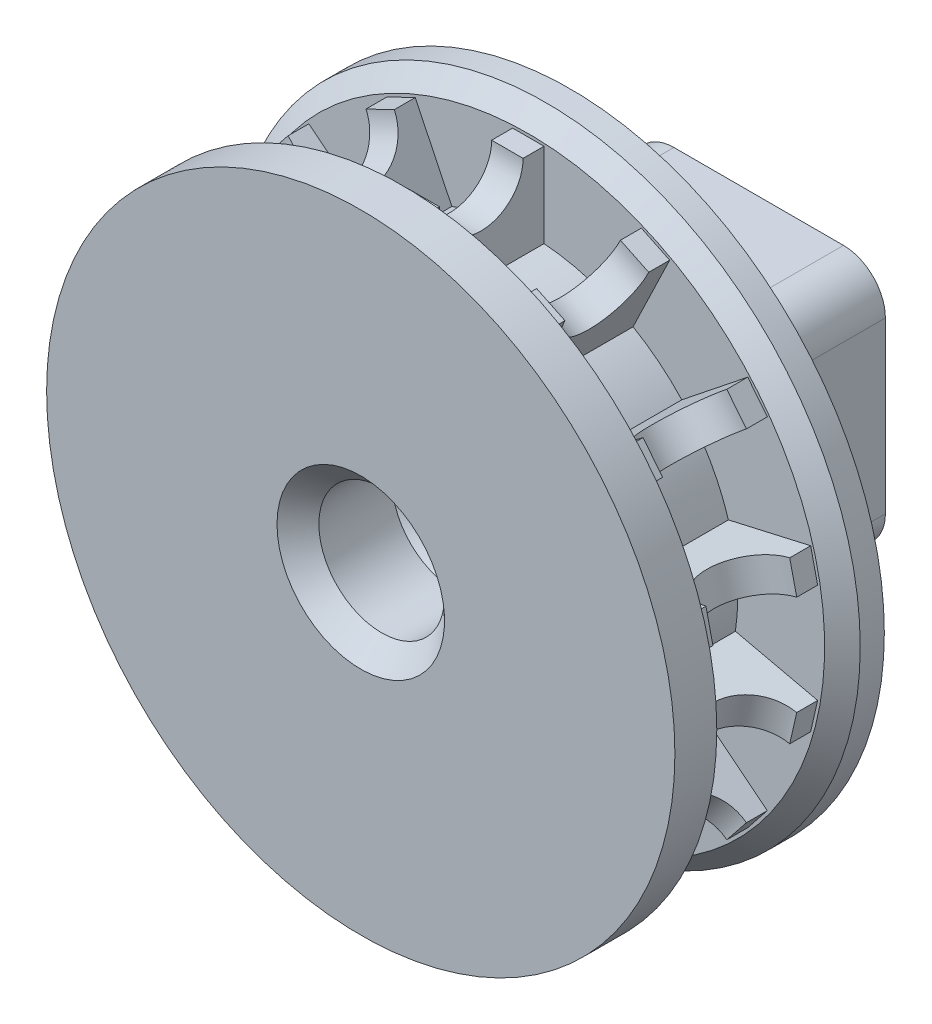
SolidWorks part; units mm, degrees
ref_plane "前基準面" through (0, 0, 0) normal (0, 0, 1) x (1, 0, 0)
ref_plane "上基準面" through (0, 0, 0) normal (0, 1, 0) x (1, 0, 0)
ref_plane "右基準面" through (0, 0, 0) normal (1, 0, 0) x (0, 0, -1)
ref_axis "基準軸1" through (0, 0, 5.5) along (0, 0, -1)
sketch "草圖1" plane through (0, 0, 0) normal (1, 0, 0) x (0, 0, -1)
  line L0 (-5, 0) -> (5, 0)
  line L1 (5, 0) -> (5, 15)
  line L2 (5, 15) -> (3, 15)
  line L3 (3, 15) -> (3, 10)
  line L4 (3, 10) -> (-3, 10)
  line L5 (-3, 10) -> (-3, 15)
  line L6 (-3, 15) -> (-5, 15)
  line L7 (-5, 15) -> (-5, 0)
  line L8 (0, 0) -> (0, 10) construction
  dimension "D1" = 10
  dimension "D2" = 2
  dimension "D3" = 15
  dimension "D4" = 10
revolve "旋轉1" add sketch "草圖1" angle 360 about L0
sketch "草圖2" plane through (0, 0, 0) normal (1, 0, 0) x (0, 0, -1)
  line L0 (-3, 10) -> (3, 10) construction
  line L1 (3, 10) -> (3, 14)
  line L2 (3, 15) -> (3, -15) construction
  line L3 (3, 14) -> (-3, 14) construction
  line L4 (-3, -15) -> (-3, 15) construction
  line L5 (-3, 14) -> (-3, 10)
  line L6 (-2, 14) -> (-3, 14)
  line L7 (2, 14) -> (3, 14)
  line L8 (-3, 10) -> (-3, 8.5)
  line L9 (-3, 8.5) -> (3, 8.5)
  line L10 (3, 8.5) -> (3, 10)
  arc A0 (-2, 14) -> (2, 14) centre (0, 14) ccw
  dimension "D2" = 2
  dimension "D1" = 4
  dimension "D3" = 1.5
extrude "填料-伸長1" add sketch "草圖2" along normal mid plane 1.5
pattern_circular "環狀複製排列1" count 14 over 360 about axis through (0, 0, 5.5) along (0, 0, -1) of "填料-伸長1"
sketch "草圖3" plane through (0, 0, -5) normal (0, 0, -1) x (-1, 0, 0)
  line L1 (-3.05, -3.05) -> (3.05, -3.05)
  line L2 (-3.05, -3.05) -> (-3.05, 3.05)
  line L3 (-3.05, 3.05) -> (3.05, 3.05)
  line L4 (3.05, -3.05) -> (3.05, 3.05)
  line L5 (-3.05, -3.05) -> (3.05, 3.05) construction
  line L6 (-3.05, 3.05) -> (3.05, -3.05) construction
  line L7 (-4.05, -6.05) -> (4.05, -6.05)
  line L8 (-6.05, -4.05) -> (-6.05, 4.05)
  line L9 (-4.05, 6.05) -> (4.05, 6.05)
  line L10 (6.05, -4.05) -> (6.05, 4.05)
  line L11 (-6.05, -6.05) -> (6.05, 6.05) construction
  line L12 (-6.05, 6.05) -> (6.05, -6.05) construction
  arc A0 (-4.05, -6.05) -> (-6.05, -4.05) centre (-4.05, -4.05) cw
  arc A1 (4.05, -6.05) -> (6.05, -4.05) centre (4.05, -4.05) ccw
  arc A2 (4.05, 6.05) -> (6.05, 4.05) centre (4.05, 4.05) cw
  arc A3 (-6.05, 4.05) -> (-4.05, 6.05) centre (-4.05, 4.05) cw
  point P0 (0, 0)
  point P6 (0, 0)
  dimension "D3" = 2
  dimension "D1" = 6.1
  dimension "D2" = 3
extrude "填料-伸長2" add sketch "草圖3" along normal blind 9
fillet "圓角1" radius 2 8 edges at (0, 6.05, -5) (-5.4642, 5.4642, -5) (-6.05, 0, -5) (-5.4642, -5.4642, -5) (0, -6.05, -5) (5.4642, -5.4642, -5) (6.05, 0, -5) (5.4642, 5.4642, -5)
chamfer "導角1" distance 0.2 angle 85 4 edges at (0, -3.05, -14) (-3.05, 0, -14) (0, 3.05, -14) (3.05, 0, -14) first distance on face at (0, 0, -14)
sketch "草圖4" plane through (0, 0, 5) normal (0, 0, 1) x (1, 0, 0)
  circle A0 centre (0, 0) radius 1.75
  dimension "D1" = 3.5
extrude "除料-伸長1" cut sketch "草圖4" against normal through all
sketch "草圖6" plane through (0, 0, 5) normal (0, 0, 1) x (1, 0, 0)
  circle A0 centre (0, 0) radius 3
  dimension "D1" = 6
extrude "除料-伸長2" cut sketch "草圖6" against normal offset from surface (6 mm away) 4 up to face at (1.75, 0, -5)
chamfer "導角2" distance 1 angle 45 1 edges at (3, 0, 5)
chamfer "導角3" distance 1.5 angle 45 1 edges at (3, 0, -1)
chamfer "導角4" distance 0.85 angle 45 1 edges at (15, 0, -3)
